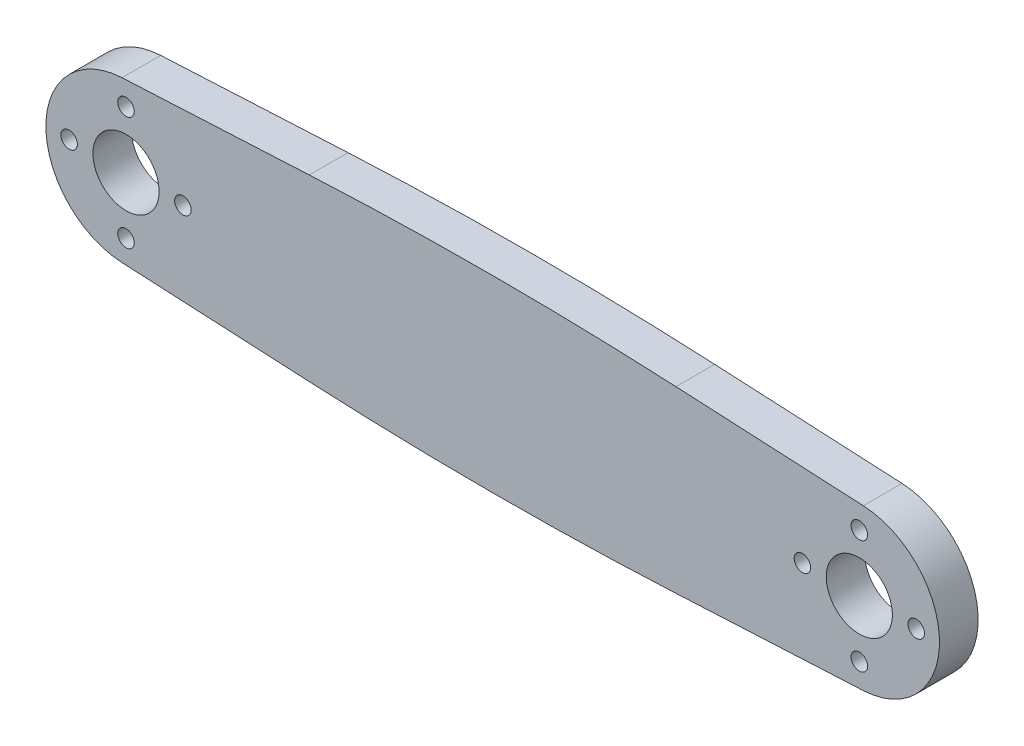
SolidWorks part; units mm, degrees
ref_plane "Front Plane" through (0, 0, 0) normal (0, 0, 1) x (1, 0, 0)
ref_plane "Top Plane" through (0, 0, 0) normal (0, 1, 0) x (1, 0, 0)
ref_plane "Right Plane" through (0, 0, 0) normal (1, 0, 0) x (0, 0, -1)
sketch "Sketch1" plane through (0, 0, 0) normal (0, 0, 1) x (1, 0, 0)
  line L0 (-45.0215, 0) -> (45.0215, 0) construction
  line L1 (0, 0) -> (0, -11.557) construction
  line L4 (-45.0215, 6.985) -> (-45.0215, -6.985) construction
  line L5 (-45.0215, 0) -> (-52.0065, 0) construction
  line L6 (0, 0) -> (0, 11.557) construction
  line L7 (45.0215, 0) -> (52.0065, 0) construction
  line L8 (45.0215, 6.985) -> (45.0215, -6.985) construction
  line L9 (-45.0215, 0) -> (-38.0365, 0) construction
  line L10 (45.0215, 0) -> (38.0365, 0) construction
  line L15 (-22.5107, 10.9899) -> (-22.5107, -10.9899) construction
  line L16 (-45.0215, 0) -> (-54.864, 0) construction
  line L17 (45.0215, 0) -> (54.864, 0) construction
  line L18 (-45.5171, 9.83) -> (-22.5107, 10.9899)
  line L19 (-45.5171, -9.83) -> (-22.5107, -10.9899)
  line L20 (22.5107, 10.9899) -> (45.5171, 9.83)
  line L21 (22.5107, -10.9899) -> (45.5171, -9.83)
  circle A2 centre (-45.0215, 0) radius 9.8425 construction
  circle A3 centre (45.0215, 0) radius 9.8425 construction
  arc A6 (22.5107, 10.9899) -> (-22.5107, 10.9899) centre (0, -435.5086) ccw
  arc A7 (-22.5107, -10.9899) -> (22.5107, -10.9899) centre (0, 435.5086) ccw
  arc A9 (45.5171, -9.83) -> (45.5171, 9.83) centre (45.0215, 0) ccw
  arc A10 (-45.5171, 9.83) -> (-45.5171, -9.83) centre (-45.0215, 0) ccw
  circle A11 centre (-45.0215, 0) radius 4.064
  circle A13 centre (45.0215, 0) radius 4.064
  circle A14 centre (-45.0215, 6.985) radius 1.016
  circle A15 centre (-38.0365, 0) radius 1.016
  circle A16 centre (-45.0215, -6.985) radius 1.016
  circle A17 centre (-52.0065, 0) radius 1.016
  circle A18 centre (45.0215, 6.985) radius 1.016
  circle A19 centre (52.0065, 0) radius 1.016
  circle A20 centre (45.0215, -6.985) radius 1.016
  circle A21 centre (38.0365, 0) radius 1.016
  dimension "D7" = 19.685
  dimension "D9" = 8.128
  dimension "D10" = 2.032
  dimension "D1" = 90.043
  dimension "D3" = 13.97
  dimension "D4" = 6.985
  dimension "D5" = 6.985
  dimension "D6" = 6.985
  dimension "D2" = 11.557
  dimension "D8" = 22.5107
extrude "Boss-Extrude1" add sketch "Sketch1" along normal blind 4.7498 contours L18 A6 L20 A9 L21 A7 L19 A10
extrude "Cut-Extrude4" cut sketch "Sketch1<4>" against normal through all and the other way through all contours A11 | A14 | A17 | A15 | A16 | A13 | A18 | A19 | A20 | A21 region at (-45.0215, 0, 0) region at (45.0215, 0, 0) region at (-45.0215, 6.985, 0) region at (-38.0365, 0, 0) region at (-45.0215, -6.985, 0) region at (-52.0065, 0, 0) region at (45.0215, 6.985, 0) region at (52.0065, 0, 0) region at (45.0215, -6.985, 0) region at (38.0365, 0, 0)
sketch "Sketch1<4>" plane through (0, 0, 0) normal (0, 0, 1) x (1, 0, 0) same geometry as "Sketch1"
ref_plane "Plane1" through (0, 0, -13.851) normal (0, 0, -1) x (-1, 0, 0)
sketch "Sketch2" plane through (0, 0, -13.851) normal (0, 0, -1) x (-1, 0, 0)
  line L0 (45.0215, 0) -> (40.643, 0) construction
  line L1 (45.0215, 0) -> (45.0215, 4.3785) construction
  circle A0 centre (45.0215, 0) radius 4.3785
  circle A1 centre (45.0215, 0) radius 4.064 construction
equation "\"D4@Sketch1\"=\"D3@Sketch1\"/2"
equation "\"D5@Sketch1\"=\"D4@Sketch1\""
equation "\"D6@Sketch1\"=\"D4@Sketch1\""
equation "\"D2@Sketch1\"=0.91/2"
equation "\"D8@Sketch1\"=\"D1@Sketch1\"/4"
